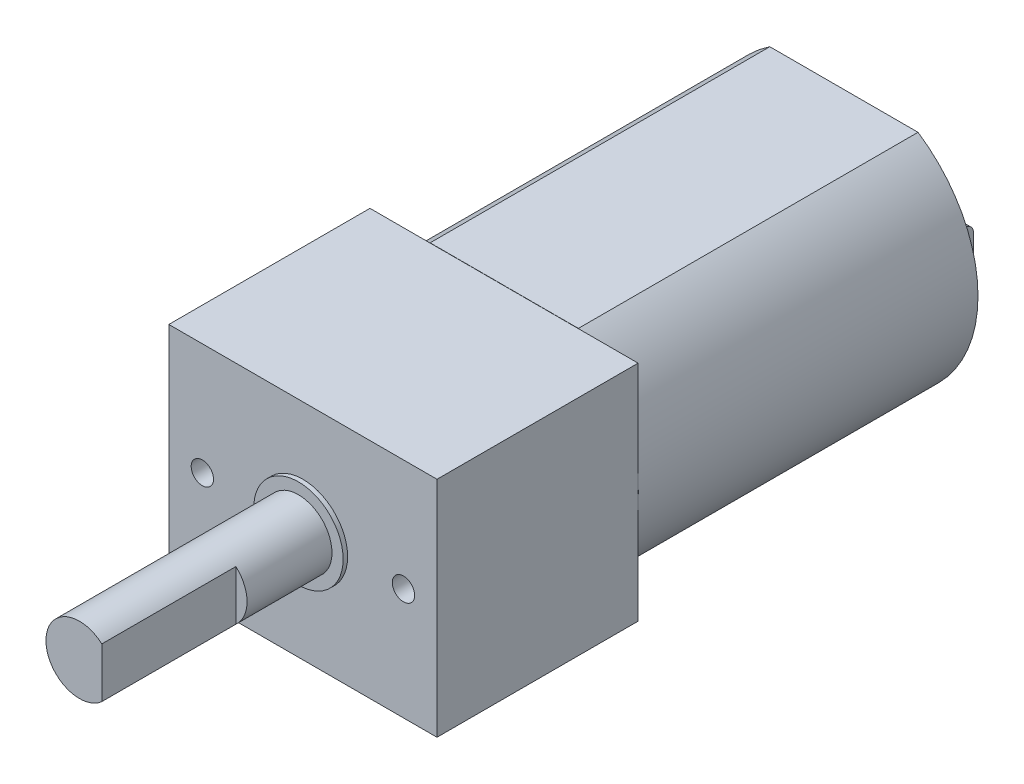
SolidWorks part; units mm, degrees
ref_plane "前视基准面" through (0, 0, 0) normal (0, 0, 1) x (1, 0, 0)
ref_plane "上视基准面" through (0, 0, 0) normal (0, 1, 0) x (1, 0, 0)
ref_plane "右视基准面" through (0, 0, 0) normal (1, 0, 0) x (0, 0, -1)
other "Configuration Table"
sketch "草图1" plane through (0, 0, 0) normal (0, 0, 1) x (1, 0, 0)
  line L0 (3.5, -0.75) -> (3.8, -0.75)
  line L1 (-6, -5) -> (6, -5)
  line L2 (-6, -5) -> (-6, 5)
  line L3 (-6, 5) -> (6, 5)
  line L4 (6, -5) -> (6, 5)
  line L5 (-6, -5) -> (6, 5) construction
  line L6 (-6, 5) -> (6, -5) construction
  line L7 (-3.8, -0.75) -> (-3.5, -0.75)
  line L8 (-3.8, -0.75) -> (-3.8, 0.75)
  line L9 (-3.8, 0.75) -> (-3.5, 0.75)
  line L10 (-3.5, -0.75) -> (-3.5, 0.75)
  line L11 (-3.8, -0.75) -> (-3.5, 0.75) construction
  line L12 (-3.8, 0.75) -> (-3.5, -0.75) construction
  line L13 (3.5, -0.75) -> (3.5, 0.75)
  line L14 (3.5, 0.75) -> (3.8, 0.75)
  line L15 (3.8, -0.75) -> (3.8, 0.75)
  line L16 (-3.5, 0) -> (3.5, 0) construction
  circle A0 centre (0, 0) radius 6
  circle A1 centre (0, 0) radius 2.5
  circle A2 centre (0, 0) radius 1.5
  point P0 (0, 0)
  point P8 (-3.65, 0)
  dimension "D6" = 5
  dimension "D7" = 3
  dimension "D1" = 12
  dimension "D2" = 10
  dimension "D3" = 0.3
  dimension "D4" = 1.5
  dimension "D5" = 7
extrude "凸台-拉伸1" add sketch "草图1" along normal blind 15.2 contours L3 A0 L1 A1 L15 L0 L13 L14 L10 L7 L8 L9 | A1 A2 | A2 | L0 L15 L14 L13 | L7 L10 L9 L8 region at (3.65, 0, 0) region at (-5.1491, -2.7634, 0) region at (-3.65, 0, 0) region at (-2.4293, 0, 0) region at (0, 0, 0)
extrude "凸台-拉伸2" add sketch "草图1<4>" against normal blind 2 contours L13 L14 L15 L0 | L8 L9 L10 L7
sketch "草图1<4>" plane through (0, 0, 0) normal (0, 0, 1) x (1, 0, 0) same geometry as "草图1"
sketch "草图2" plane through (3.8, 0, 0) normal (1, 0, 0) x (0, 0, -1)
  line L0 (0.95, 0) -> (1.05, 0) construction
  line L1 (0.95, 0.45) -> (1.05, 0.45)
  line L2 (0.95, -0.45) -> (1.05, -0.45)
  line L4 (1, 0.75) -> (1, -0.75) construction
  line L5 (2, 0.75) -> (0, 0.75) construction
  line L6 (2, -0.75) -> (0, -0.75) construction
  arc A0 (0.95, 0.45) -> (0.95, -0.45) centre (0.95, 0) ccw
  arc A1 (1.05, -0.45) -> (1.05, 0.45) centre (1.05, 0) ccw
  point P3 (1, 0)
  dimension "D2" = 0.45
  dimension "D1" = 0.1
extrude "切除-拉伸2" cut sketch "草图2" against normal through all
fillet "圆角1" radius 0.4 4 edges at (-3.65, 0.75, -2) (-3.65, -0.75, -2) (3.65, 0.75, -2) (3.65, -0.75, -2)
extrude "凸台-拉伸3" add sketch "草图1<5>" against normal blind 1.2 contours A1 A2 | A2 region at (-2.4293, 0, 0) region at (0, 0, 0)
sketch "草图1<5>" plane through (0, 0, 0) normal (0, 0, 1) x (1, 0, 0) same geometry as "草图1"
extrude "切除-拉伸1" cut sketch "草图1<7>" along normal blind 0.6 from surface contours A2 region at (0, 0, 0) starting at face at (2.5, 0, -1.2)
sketch "草图1<7>" plane through (0, 0, 0) normal (0, 0, 1) x (1, 0, 0) same geometry as "草图1"
fillet "圆角2" radius 0.4 1 edges at (2.5, 0, -1.2)
sketch "草图3" plane through (0, 0, 15.2) normal (0, 0, 1) x (1, 0, 0)
  circle A0 centre (0, 0) radius 2
  circle A1 centre (0, 0) radius 0.5
  dimension "D1" = 4
  dimension "D2" = 1
extrude "凸台-拉伸4" add sketch "草图3" along normal blind 0.5 contours A0
extrude "凸台-拉伸5" add sketch "草图3<3>" along normal blind 3 contours A1 region at (0, 0, 15.2)
sketch "草图3<3>" plane through (0, 0, 15.2) normal (0, 0, 1) x (1, 0, 0) same geometry as "草图3"
sketch "草图4" plane through (0, 0, 15.2) normal (0, 0, 1) x (1, 0, 0)
  line L0 (-4.25, 0) -> (4.25, 0) construction
  line L1 (0, 0) -> (0, 5) construction
  line L2 (-3.3166, 5) -> (3.3166, 5) construction
  circle A0 centre (-4.25, 0) radius 0.7
  circle A1 centre (4.25, 0) radius 0.7
  circle A2 centre (0, 3.5) radius 0.5
  dimension "D1" = 1.4
  dimension "D2" = 8.5
  dimension "D3" = 1
  dimension "D4" = 3.5
extrude "切除-拉伸3" cut sketch "草图4" against normal blind 1
sketch "草图5" plane through (0, 0, 15.2) normal (0, 0, 1) x (1, 0, 0)
  line L1 (-6, -5) -> (6, -5)
  line L2 (-6, -5) -> (-6, 5)
  line L3 (-6, 5) -> (6, 5)
  line L4 (6, -5) -> (6, 5)
  line L5 (-6, -5) -> (6, 5) construction
  line L6 (-6, 5) -> (6, -5) construction
  point P0 (0, 0)
  dimension "D1" = 12
  dimension "D2" = 10
extrude "凸台-拉伸6" add sketch "草图5" along normal blind 9 from offset 0.01 contours L2 L3 L4 L1
sketch "草图6" plane through (0, 0, 24.21) normal (0, 0, 1) x (1, 0, 0)
  line L0 (1, 1.118) -> (1, -1.118)
  circle A0 centre (0, 0) radius 2
  circle A1 centre (0, 0) radius 1.5
  dimension "D2" = 4
  dimension "D3" = 3
  dimension "D1" = 1
extrude "凸台-拉伸7" add sketch "草图6" along normal blind 0.2 contours A0
extrude "凸台-拉伸8" add sketch "草图6<4>" along normal blind 4 contours A1
sketch "草图6<4>" plane through (0, 0, 24.21) normal (0, 0, 1) x (1, 0, 0) same geometry as "草图6"
extrude "凸台-拉伸9" add sketch "草图6<5>" along normal blind 6 from surface contours L0 A1 region at (-0.148, 0, 24.21) starting at face at (1.5, 0, 28.21)
sketch "草图6<5>" plane through (0, 0, 24.21) normal (0, 0, 1) x (1, 0, 0) same geometry as "草图6"
sketch "草图7" plane through (0, 0, 24.21) normal (0, 0, 1) x (1, 0, 0)
  line L0 (-4.5, 0) -> (4.5, 0) construction
  circle A0 centre (-4.5, 0) radius 0.5
  circle A1 centre (4.5, 0) radius 0.5
  dimension "D2" = 1
  dimension "D3" = 1
  dimension "D1" = 9
extrude "切除-拉伸5" cut sketch "草图7" against normal blind 5.8 contours A0 | A1
